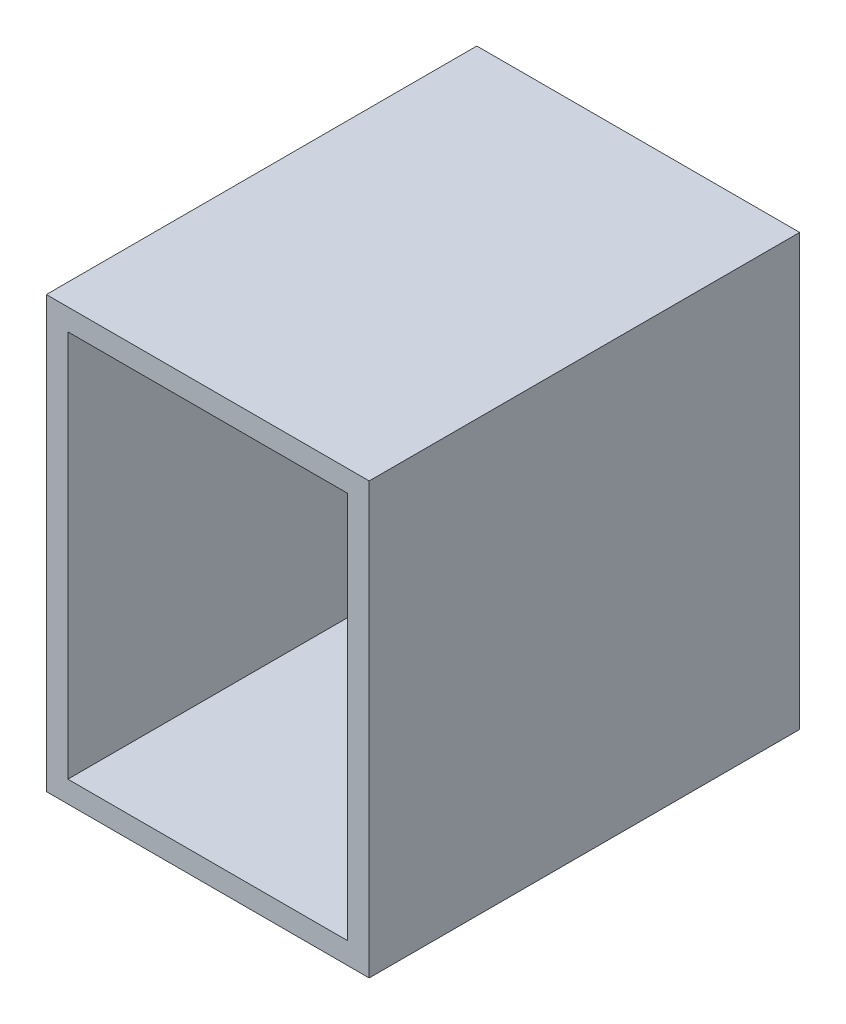
SolidWorks part; units mm, degrees
material "1060 合金"
ref_plane "前视基准面" through (0, 0, 0) normal (0, 0, 1) x (1, 0, 0)
ref_plane "上视基准面" through (0, 0, 0) normal (0, 1, 0) x (1, 0, 0)
ref_plane "右视基准面" through (0, 0, 0) normal (1, 0, 0) x (0, 0, -1)
other "Configuration Table"
sketch "草图1" plane through (0, 0, 0) normal (0, 0, 1) x (1, 0, 0)
  line L1 (0, 0) -> (15, 0)
  line L2 (0, 0) -> (0, -20)
  line L3 (0, -20) -> (15, -20)
  line L4 (15, 0) -> (15, -20)
  dimension "D1" = 20
  dimension "D2" = 15
extrude "拉伸-薄壁1" add sketch "草图1" along normal blind 20 thin thin type one direction reverse wall 1
sketch "草图2" plane through (0, -20, 0) normal (0, -1, 0) x (1, 0, 0)
  circle A1 centre (7.5, 825) radius 2.6
  circle A2 centre (7.5, 825) radius 2.6
  dimension "D1" = 0
extrude "切除-拉伸1" [suppressed] cut sketch "草图2" against normal up to next
